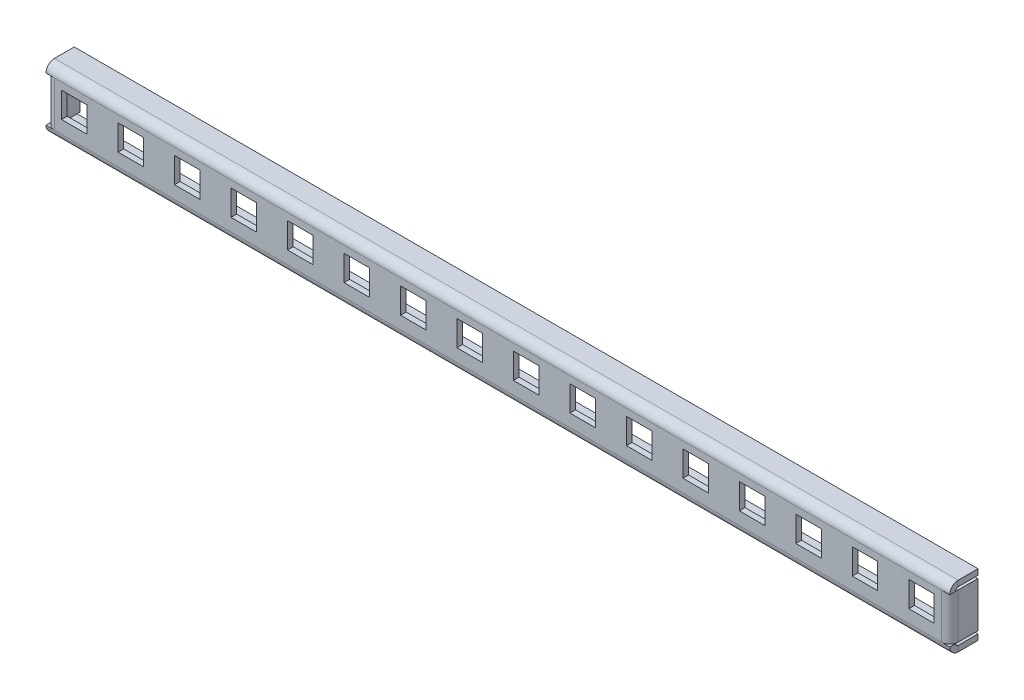
SolidWorks part; units mm, degrees
note: The reader was unsure of these and kept them because the rebuilt part matched: thickness of "基体-法兰1", "边线-法兰1", "边线-法兰2", "钣金6", "钣金7", "钣金8", "钣金9", "钣金10"; flange length of "边线-法兰1", "边线-法兰2".
material "普通碳钢"
ref_plane "前视基准面" through (0, 0, 0) normal (0, 0, 1) x (1, 0, 0)
ref_plane "上视基准面" through (0, 0, 0) normal (0, 1, 0) x (1, 0, 0)
ref_plane "右视基准面" through (0, 0, 0) normal (1, 0, 0) x (0, 0, -1)
sketch "草图1" plane through (0, 0, 0) normal (0, 0, 1) x (1, 0, 0)
  line L1 (-160, 11) -> (160, 11)
  line L2 (-160, 11) -> (-160, -11)
  line L3 (-160, -11) -> (160, -11)
  line L4 (160, 11) -> (160, -11)
  line L5 (-160, 11) -> (160, -11) construction
  line L6 (-160, -11) -> (160, 11) construction
  point P0 (0, 0)
  dimension "D1" = 320
  dimension "D2" = 22
base flange "基体-法兰1" sketch "草图1" thickness 2 reverse thickness direction no parameters "D1"=1
edge flange "边线-法兰1" sketch "草图10" flange profiles "草图10", "草图11" flange angle 90 flange length 10 flange position material inside bend radius 1 thickness 2 relief rectangular parameters "D6"=10, "D8"=0.2
sketch "草图10" plane through (0, -11, -2) normal (0, 1, 0) x (1, 0, 0)
  line L1 (160, 0) -> (-160, 0) construction
  line L2 (-160, 0) -> (-160, 8)
  line L3 (-160, 8) -> (160, 8)
  line L4 (160, 8) -> (160, 0)
  line L5 (160, 0) -> (-160, 0)
  dimension "D1" = 8
sketch "草图11" plane through (0, 11, -2) normal (0, -1, 0) x (-1, 0, 0)
  line L0 (160, 0) -> (-160, 0) construction
  line L1 (160, 0) -> (-160, 0)
  line L2 (160, 0) -> (160, 8)
  line L3 (160, 8) -> (-160, 8)
  line L4 (-160, 8) -> (-160, 0)
bend "边线折弯1" bend radius 1 bend angle 90 parameters "D5"=1
bend "边线折弯2" bend radius 1 bend angle 90 parameters "D5"=2
edge flange "边线-法兰2" sketch "草图16" flange profiles "草图16", "草图17" flange angle 90 flange length 10 flange position material inside bend radius 1 thickness 2 relief none parameters "D6"=10, "D8"=0.2
sketch "草图16" plane through (-160, 0, -2) normal (1, 0, 0) x (0, -1, 0)
  line L1 (8, 0) -> (-8, 0) construction
  line L2 (-8, 0) -> (-8, 8)
  line L3 (-8, 8) -> (8, 8)
  line L4 (8, 8) -> (8, 0)
  line L5 (8, 0) -> (-8, 0)
  dimension "D1" = 8
sketch "草图17" plane through (160, 0, -2) normal (-1, 0, 0) x (0, 1, 0)
  line L0 (8, 0) -> (-8, 0) construction
  line L1 (8, 0) -> (-8, 0)
  line L2 (8, 0) -> (8, 8)
  line L3 (8, 8) -> (-8, 8)
  line L4 (-8, 8) -> (-8, 0)
bend "边线折弯3" bend radius 1 bend angle 90 parameters "D5"=3
bend "边线折弯4" bend radius 1 bend angle 90 parameters "D5"=4
sketch "草图18" plane through (0, 0, 0) normal (0, 0, 1) x (1, 0, 0)
  line L0 (160, 11) -> (-160, 11) construction
  line L5 (-154.5, 5.5) -> (-145.5, 5.5)
  line L6 (-154.5, 5.5) -> (-154.5, -3.5)
  line L7 (-154.5, -3.5) -> (-145.5, -3.5)
  line L8 (-145.5, 5.5) -> (-145.5, -3.5)
  line L9 (-154.5, 5.5) -> (-145.5, -3.5) construction
  line L10 (-154.5, -3.5) -> (-145.5, 5.5) construction
  point P0 (-150, 1)
  dimension "D1" = 150
  dimension "D2" = 9
  dimension "D3" = 9
  dimension "D4" = 10
extrude "切除-拉伸1" cut sketch "草图18" against normal blind 10 normal cut yes
pattern_linear "阵列(线性)1" count 20 spacing 20 along (1, 0, 0) of "切除-拉伸1"
sketch "折弯-线1" [suppressed] plane through (0, 0, 0) normal (0, 1, 0) x (1, 0, 0)
sketch "边界框1" [suppressed] plane through (0, 0, 0) normal (0, 1, 0) x (1, 0, 0)
sheet metal parameters "钣金6" thickness 2 parameters "D1"=1, "D7"=1
flat pattern "平板型式6" [suppressed]
sketch "折弯-线2" plane through (0, 0, 0) normal (0, 1, 0) x (1, 0, 0)
sketch "边界框2" [suppressed] plane through (0, 0, 0) normal (0, 1, 0) x (1, 0, 0)
sheet metal parameters "钣金7" thickness 2 parameters "D1"=1, "D7"=1
flat pattern "平板型式6" [suppressed]
sketch "折弯-线2" plane through (0, 0, 0) normal (0, 1, 0) x (1, 0, 0)
sketch "边界框2" [suppressed] plane through (0, 0, 0) normal (0, 1, 0) x (1, 0, 0)
bend of the flat pattern "展开-<边线折弯1>1"
bend of the flat pattern "展开-<边线折弯2>1"
sheet metal parameters "钣金8" thickness 2 parameters "D1"=1, "D7"=1
flat pattern "平板型式6" [suppressed]
sketch "折弯-线2" plane through (0, 0, 0) normal (0, 1, 0) x (1, 0, 0)
sketch "边界框2" [suppressed] plane through (0, 0, 0) normal (0, 1, 0) x (1, 0, 0)
bend of the flat pattern "展开-<边线折弯1>1"
bend of the flat pattern "展开-<边线折弯2>1"
bend of the flat pattern "展开-<边线折弯3>1"
bend of the flat pattern "展开-<边线折弯4>1"
sheet metal parameters "钣金9" thickness 2 parameters "D1"=1, "D7"=1
flat pattern "平板型式6" [suppressed]
sketch "折弯-线2" plane through (0, 0, 0) normal (0, 1, 0) x (1, 0, 0)
sketch "边界框2" [suppressed] plane through (0, 0, 0) normal (0, 1, 0) x (1, 0, 0)
bend of the flat pattern "展开-<边线折弯1>1"
bend of the flat pattern "展开-<边线折弯2>1"
bend of the flat pattern "展开-<边线折弯3>1"
bend of the flat pattern "展开-<边线折弯4>1"
sheet metal parameters "钣金10" thickness 2 parameters "D1"=1, "D7"=1
flat pattern "平板型式6"
sketch "折弯-线2" plane through (0, 0, 0) normal (0, 0, 1) x (1, 0, 0)
  line L0 (294.1, -47.5) -> (294.1, 47.5) construction
  line L1 (-294.1, 47.5) -> (-294.1, -47.5) construction
  line L2 (295, 49.1) -> (-295, 49.1) construction
  line L3 (-295, -49.1) -> (295, -49.1) construction
  line L4 (294.1, -47.5) -> (294.1, 47.5) construction
  line L5 (-294.1, 47.5) -> (-294.1, -47.5) construction
  line L6 (295, 49.1) -> (-295, 49.1) construction
  line L7 (-295, -49.1) -> (295, -49.1) construction
sketch3d "边界框2" [suppressed]
  line L0 (-313.2, -56.2, 0) -> (313.2, -56.2, 0) construction
  line L1 (-313.2, 56.2, 0) -> (313.2, 56.2, 0) construction
  line L2 (-313.2, -56.2, 0) -> (-313.2, 56.2, 0) construction
  line L3 (313.2, -56.2, 0) -> (313.2, 56.2, 0) construction
bend of the flat pattern "展开-<边线折弯1>1"
bend of the flat pattern "展开-<边线折弯2>1"
bend of the flat pattern "展开-<边线折弯3>1"
bend of the flat pattern "展开-<边线折弯4>1"
